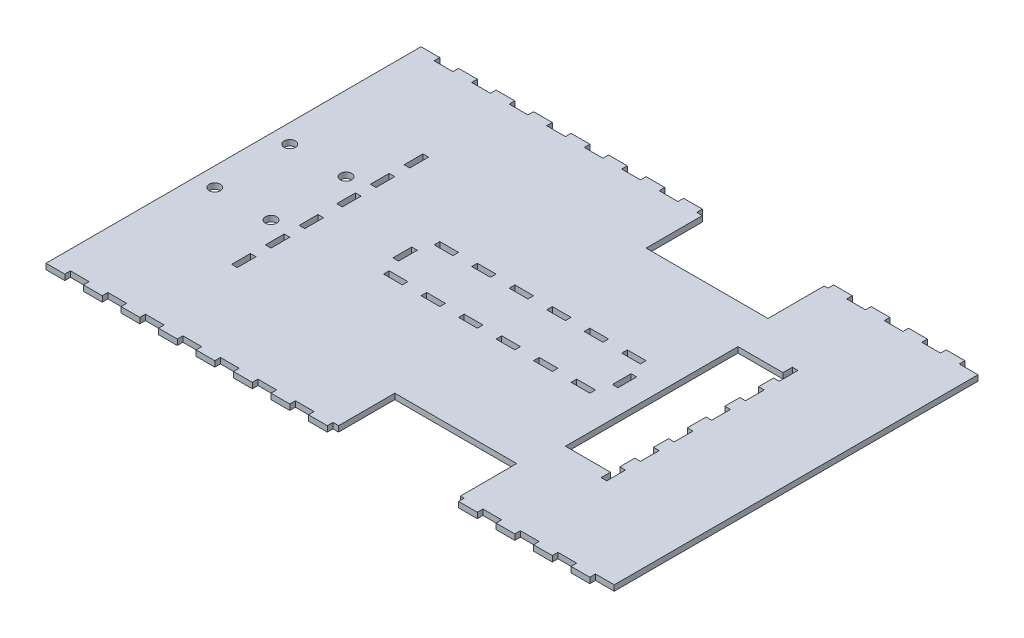
SolidWorks part; units mm, degrees
ref_plane "Front Plane" through (0, 0, 0) normal (0, 0, 1) x (1, 0, 0)
ref_plane "Top Plane" through (0, 0, 0) normal (0, 1, 0) x (1, 0, 0)
ref_plane "Right Plane" through (0, 0, 0) normal (1, 0, 0) x (0, 0, -1)
sketch "Sketch3" plane through (0, 0, 0) normal (0, 1, 0) x (1, 0, 0)
  line L0 (0, 0) -> (-300, 0) construction
  line L1 (-300, -97) -> (-300, 97)
  line L2 (-290, 100) -> (-300, 100)
  line L3 (-290, 97) -> (-290, 100)
  line L4 (-280, 97) -> (-290, 97)
  line L5 (-300, 100) -> (-300, 97)
  line L6 (-270, 100) -> (-280, 100)
  line L7 (-270, 97) -> (-270, 100)
  line L8 (-260, 97) -> (-270, 97)
  line L9 (-280, 100) -> (-280, 97)
  line L10 (-250, 100) -> (-260, 100)
  line L11 (-250, 97) -> (-250, 100)
  line L12 (-240, 97) -> (-250, 97)
  line L13 (-260, 100) -> (-260, 97)
  line L14 (-150, -100) -> (-150, 100) construction
  line L15 (-230, 100) -> (-240, 100)
  line L16 (-230, 97) -> (-230, 100)
  line L17 (-220, 97) -> (-230, 97)
  line L18 (-240, 100) -> (-240, 97)
  line L19 (-210, 100) -> (-220, 100)
  line L20 (-210, 97) -> (-210, 100)
  line L21 (-200, 97) -> (-210, 97)
  line L22 (-10, 100) -> (-20, 100)
  line L23 (0, -97) -> (0, 97)
  line L24 (-10, 97) -> (-10, 100)
  line L25 (-50, -46) -> (-50, 46) construction
  line L26 (-247, 23) -> (-250, 23)
  line L27 (-247, 5) -> (-250, 5)
  line L28 (-247, 48.5) -> (-247, -48.5) construction
  line L29 (-247, 48.5) -> (-223, 48.5) construction
  line L30 (-223, 48.5) -> (-223, -48.5) construction
  line L31 (-210, 15) -> (-90, 15) construction
  line L32 (-90, 15) -> (-90, 5) construction
  line L33 (0, 97) -> (-10, 97)
  line L34 (-220, 100) -> (-220, 97)
  line L35 (-190, 100) -> (-200, 100)
  line L36 (-190, 97) -> (-190, 100)
  line L37 (-180, 97) -> (-190, 97)
  line L38 (-200, 100) -> (-200, 97)
  line L39 (-170, 100) -> (-180, 100)
  line L40 (-170, 97) -> (-170, 100)
  line L41 (-160, 97) -> (-170, 97)
  line L42 (-180, 100) -> (-180, 97)
  line L43 (-150, 100) -> (-160, 100)
  line L44 (-150, 97) -> (-150, 100)
  line L45 (-140, 97) -> (-150, 97)
  line L46 (-160, 100) -> (-160, 97)
  line L47 (-130, 100) -> (-140, 100)
  line L48 (-130, 97) -> (-130, 100)
  line L49 (-120, 97) -> (-130, 97)
  line L50 (-140, 100) -> (-140, 97)
  line L51 (-110, 100) -> (-120, 100)
  line L52 (-110, 97) -> (-110, 100)
  line L53 (-100, 97) -> (-110, 97)
  line L54 (-120, 100) -> (-120, 97)
  line L55 (-90, 100) -> (-100, 100)
  line L56 (-90, 97) -> (-90, 100)
  line L57 (-80, 97) -> (-90, 97)
  line L58 (-100, 100) -> (-100, 97)
  line L59 (-70, 100) -> (-80, 100)
  line L60 (-70, 97) -> (-70, 100)
  line L61 (-60, 97) -> (-70, 97)
  line L62 (-80, 100) -> (-80, 97)
  line L63 (-50, 100) -> (-60, 100)
  line L64 (-50, 97) -> (-50, 100)
  line L65 (-40, 97) -> (-50, 97)
  line L66 (-60, 100) -> (-60, 97)
  line L67 (-30, 100) -> (-40, 100)
  line L68 (-210, -15) -> (-90, -15) construction
  line L69 (-30, 97) -> (-30, 100)
  line L70 (-53, -23) -> (-50, -23)
  line L71 (-20, -100) -> (-20, -97)
  line L72 (-40, -100) -> (-40, -97)
  line L73 (-20, -97) -> (-30, -97)
  line L74 (-30, -97) -> (-30, -100)
  line L75 (-30, -100) -> (-40, -100)
  line L76 (-60, -100) -> (-60, -97)
  line L77 (-40, -97) -> (-50, -97)
  line L78 (-50, -97) -> (-50, -100)
  line L79 (-50, -100) -> (-60, -100)
  line L80 (-80, -100) -> (-80, -97)
  line L81 (-60, -97) -> (-70, -97)
  line L82 (-70, -97) -> (-70, -100)
  line L83 (-70, -100) -> (-80, -100)
  line L84 (-100, -100) -> (-100, -97)
  line L85 (-80, -97) -> (-90, -97)
  line L86 (-90, -97) -> (-90, -100)
  line L87 (-90, -100) -> (-100, -100)
  line L88 (-120, -100) -> (-120, -97)
  line L89 (-100, -97) -> (-110, -97)
  line L90 (-110, -97) -> (-110, -100)
  line L91 (-110, -100) -> (-120, -100)
  line L92 (-140, -100) -> (-140, -97)
  line L93 (-120, -97) -> (-130, -97)
  line L94 (-130, -97) -> (-130, -100)
  line L95 (-130, -100) -> (-140, -100)
  line L96 (-160, -100) -> (-160, -97)
  line L97 (-140, -97) -> (-150, -97)
  line L98 (-150, -97) -> (-150, -100)
  line L99 (-150, -100) -> (-160, -100)
  line L100 (-180, -100) -> (-180, -97)
  line L101 (-160, -97) -> (-170, -97)
  line L102 (-170, -97) -> (-170, -100)
  line L103 (-170, -100) -> (-180, -100)
  line L104 (-200, -100) -> (-200, -97)
  line L105 (-180, -97) -> (-190, -97)
  line L106 (-190, -97) -> (-190, -100)
  line L107 (-190, -100) -> (-200, -100)
  line L108 (-247, -48.5) -> (-223, -48.5) construction
  line L109 (-247, 5) -> (-247, 15)
  line L110 (-220, -100) -> (-220, -97)
  line L111 (0, -97) -> (-10, -97)
  line L112 (-10, -97) -> (-10, -100)
  line L113 (-10, -100) -> (-20, -100)
  line L114 (-200, -97) -> (-210, -97)
  line L115 (-210, -97) -> (-210, -100)
  line L116 (-210, -100) -> (-220, -100)
  line L117 (-240, -100) -> (-240, -97)
  line L118 (-220, -97) -> (-230, -97)
  line L119 (-230, -97) -> (-230, -100)
  line L120 (-230, -100) -> (-240, -100)
  line L121 (-53, -5) -> (-50, -5)
  line L122 (-260, -100) -> (-260, -97)
  line L123 (-240, -97) -> (-250, -97)
  line L124 (-250, -97) -> (-250, -100)
  line L125 (-250, -100) -> (-260, -100)
  line L126 (-280, -100) -> (-280, -97)
  line L127 (-260, -97) -> (-270, -97)
  line L128 (-270, -97) -> (-270, -100)
  line L129 (-270, -100) -> (-280, -100)
  line L130 (-300, -100) -> (-300, -97)
  line L131 (-210, 15) -> (-210, -15) construction
  line L132 (-115, 15) -> (-125, 15)
  line L133 (-90, 5) -> (-93, 5)
  line L134 (-90, 5) -> (-90, -5)
  line L135 (-90, -5) -> (-93, -5)
  line L136 (-93, 5) -> (-93, -5)
  line L137 (-95, 15) -> (-105, 15)
  line L138 (-95, 15) -> (-95, 12)
  line L139 (-95, 12) -> (-105, 12)
  line L140 (-105, 15) -> (-105, 12)
  line L141 (-115, 12) -> (-125, 12)
  line L142 (-125, 15) -> (-125, 12)
  line L143 (-135, 15) -> (-145, 15)
  line L144 (-135, 12) -> (-145, 12)
  line L145 (-145, 15) -> (-145, 12)
  line L146 (-155, 15) -> (-165, 15)
  line L147 (-155, 12) -> (-165, 12)
  line L148 (-165, 15) -> (-165, 12)
  line L149 (-175, 15) -> (-185, 15)
  line L150 (-175, 12) -> (-185, 12)
  line L151 (-185, 15) -> (-185, 12)
  line L152 (-195, 15) -> (-205, 15)
  line L153 (-195, 12) -> (-205, 12)
  line L154 (-205, 15) -> (-205, 12)
  line L155 (-195, 12) -> (-195, 15)
  line L156 (-175, 12) -> (-175, 15)
  line L157 (-155, 12) -> (-155, 15)
  line L158 (-135, 12) -> (-135, 15)
  line L159 (-115, 12) -> (-115, 15)
  line L160 (-207, 5) -> (-207, -5)
  line L161 (-210, -5) -> (-207, -5)
  line L162 (-210, 5) -> (-210, -5)
  line L163 (-210, 5) -> (-207, 5)
  line L164 (-115, -12) -> (-115, -15)
  line L165 (-135, -12) -> (-135, -15)
  line L166 (-155, -12) -> (-155, -15)
  line L167 (-175, -12) -> (-175, -15)
  line L168 (-195, -12) -> (-195, -15)
  line L169 (-205, -15) -> (-205, -12)
  line L170 (-195, -12) -> (-205, -12)
  line L171 (-195, -15) -> (-205, -15)
  line L172 (-185, -15) -> (-185, -12)
  line L173 (-175, -12) -> (-185, -12)
  line L174 (-175, -15) -> (-185, -15)
  line L175 (-165, -15) -> (-165, -12)
  line L176 (-155, -12) -> (-165, -12)
  line L177 (-155, -15) -> (-165, -15)
  line L178 (-145, -15) -> (-145, -12)
  line L179 (-135, -12) -> (-145, -12)
  line L180 (-135, -15) -> (-145, -15)
  line L181 (-125, -15) -> (-125, -12)
  line L182 (-115, -12) -> (-125, -12)
  line L183 (-105, -15) -> (-105, -12)
  line L184 (-95, -12) -> (-105, -12)
  line L185 (-95, -15) -> (-95, -12)
  line L186 (-95, -15) -> (-105, -15)
  line L187 (-115, -15) -> (-125, -15)
  line L188 (-247, 15) -> (-250, 15)
  line L189 (-250, 5) -> (-250, 15)
  line L190 (-247, 23) -> (-247, 33)
  line L191 (-247, 33) -> (-250, 33)
  line L192 (-250, 23) -> (-250, 33)
  line L193 (-247, 41) -> (-250, 41)
  line L194 (-247, 41) -> (-247, 51)
  line L195 (-247, 51) -> (-250, 51)
  line L196 (-250, 41) -> (-250, 51)
  line L197 (-250, -41) -> (-250, -51)
  line L198 (-247, -51) -> (-250, -51)
  line L199 (-247, -41) -> (-247, -51)
  line L200 (-247, -41) -> (-250, -41)
  line L201 (-250, -23) -> (-250, -33)
  line L202 (-247, -33) -> (-250, -33)
  line L203 (-247, -23) -> (-247, -33)
  line L204 (-250, -5) -> (-250, -15)
  line L205 (-247, -15) -> (-250, -15)
  line L206 (-247, -5) -> (-247, -15)
  line L207 (-247, -5) -> (-250, -5)
  line L208 (-247, -23) -> (-250, -23)
  line L209 (-53, -5) -> (-53, -15)
  line L210 (-53, -15) -> (-50, -15)
  line L211 (-50, -5) -> (-50, -15)
  line L212 (-53, -23) -> (-53, -33)
  line L213 (-53, -33) -> (-50, -33)
  line L214 (-50, -23) -> (-50, -33)
  line L215 (-53, -41) -> (-50, -41)
  line L216 (-53, -41) -> (-53, -51)
  line L217 (-53, -51) -> (-50, -51)
  line L218 (-50, -41) -> (-50, -51)
  line L219 (-50, 41) -> (-50, 51)
  line L220 (-53, 51) -> (-50, 51)
  line L221 (-53, 41) -> (-53, 51)
  line L222 (-53, 41) -> (-50, 41)
  line L223 (-50, 23) -> (-50, 33)
  line L224 (-53, 33) -> (-50, 33)
  line L225 (-53, 23) -> (-53, 33)
  line L226 (-50, 5) -> (-50, 15)
  line L227 (-53, 15) -> (-50, 15)
  line L228 (-53, 5) -> (-53, 15)
  line L229 (-53, 5) -> (-50, 5)
  line L230 (-53, 23) -> (-50, 23)
  line L231 (-280, -97) -> (-290, -97)
  line L232 (-290, -97) -> (-290, -100)
  line L233 (-290, -100) -> (-300, -100)
  line L234 (-20, 97) -> (-30, 97)
  line L235 (-40, 100) -> (-40, 97)
  line L236 (-20, 100) -> (-20, 97)
  circle A0 centre (-290, 20) radius 3
  circle A1 centre (-260, 20) radius 3
  circle A2 centre (-260, -20) radius 3
  circle A3 centre (-290, -20) radius 3
  point P80 (-91.5, 0)
  point P82 (-150, 0)
  point P126 (-223, 0)
  point P127 (-250, 0)
  point P129 (-50, 0)
  point P150 (-150, -15)
  point P151 (-150, 15)
  point P183 (-208.5, 0)
  point P212 (-223, 18)
  point P213 (-250, 18)
  point P218 (-223, 36)
  point P219 (-250, 36)
  point P233 (-250, -36)
  point P234 (-250, -18)
  point P257 (-50, -18)
  point P258 (-50, -36)
  point P259 (-50, 36)
  point P260 (-50, 18)
  dimension "D17" = 6
  dimension "D18" = 6
  dimension "D1" = 300
  dimension "D4" = 97
  dimension "D5" = 100
  dimension "D6" = 97
  dimension "D7" = 10
  dimension "D8" = 97
  dimension "D9" = 3
  dimension "D10" = 5
  dimension "D11" = 48.5
  dimension "D12" = 24
  dimension "D13" = 60
  dimension "D14" = 15
  dimension "D15" = 30
  dimension "D16" = 20
  dimension "D29" = 10
  dimension "D30" = 3
  dimension "D31" = 10
  dimension "D32" = 3
  dimension "D33" = 10
  dimension "D34" = 5
  dimension "D37" = 3
  dimension "D38" = 15
  dimension "D35" = 6
  dimension "D36" = 3
extrude "Boss-Extrude1" add sketch "Sketch3" along normal blind 3 contours L1 L116 L115 L107 L106 L83 L82 L79 L74 L75 L95 L98 L99 L91 L90 L86 region at (-149.8344, 0, 0)
sketch "Sketch4" plane through (0, 3, 0) normal (0, 1, 0) x (1, 0, 0)
  line L0 (-53, 5) -> (-53, 15) construction
  line L1 (-53, 46) -> (-77, 46)
  line L2 (-53, 46) -> (-53, -46)
  line L3 (-53, -46) -> (-77, -46)
  line L4 (-77, 46) -> (-77, -46)
  line L5 (-90, 0) -> (0, 0) construction
  line L6 (-90, 5) -> (-90, -5) construction
  dimension "D1" = 92
  dimension "D2" = 24
  dimension "D3" = 46
extrude "Cut-Extrude1" cut sketch "Sketch4" against normal blind 10
sketch "Sketch5" plane through (0, 3, 0) normal (0, 1, 0) x (1, 0, 0)
  line L0 (-82, 0) -> (-82, 67) construction
  line L1 (-77, 46) -> (-77, -46) construction
  line L2 (-82, 67) -> (-147, 67)
  line L3 (-82, 67) -> (-82, 97)
  line L4 (-82, 97) -> (-147, 97)
  line L5 (-147, 67) -> (-147, 97)
  line L6 (-82, 97) -> (-82, 117.024)
  line L7 (-110, 100) -> (-120, 100) construction
  line L8 (-82, 0) -> (-300, 0) construction
  line L9 (-300, 100) -> (-300, -100) construction
  line L10 (-147, -67) -> (-147, -97)
  line L11 (-82, -97) -> (-147, -97)
  line L12 (-82, -67) -> (-82, -97)
  line L13 (-82, -67) -> (-147, -67)
  dimension "D1" = 5
  dimension "D2" = 30
  dimension "D3" = 3
  dimension "D4" = 65
extrude "Cut-Extrude2" cut sketch "Sketch5" against normal blind 10 contours L5 L2 L3 L4 | L12 L13 L10 L11 region at (-114.5, 3, -82) region at (-114.5, 3, 82) body kept at (-300, 0, -100)
